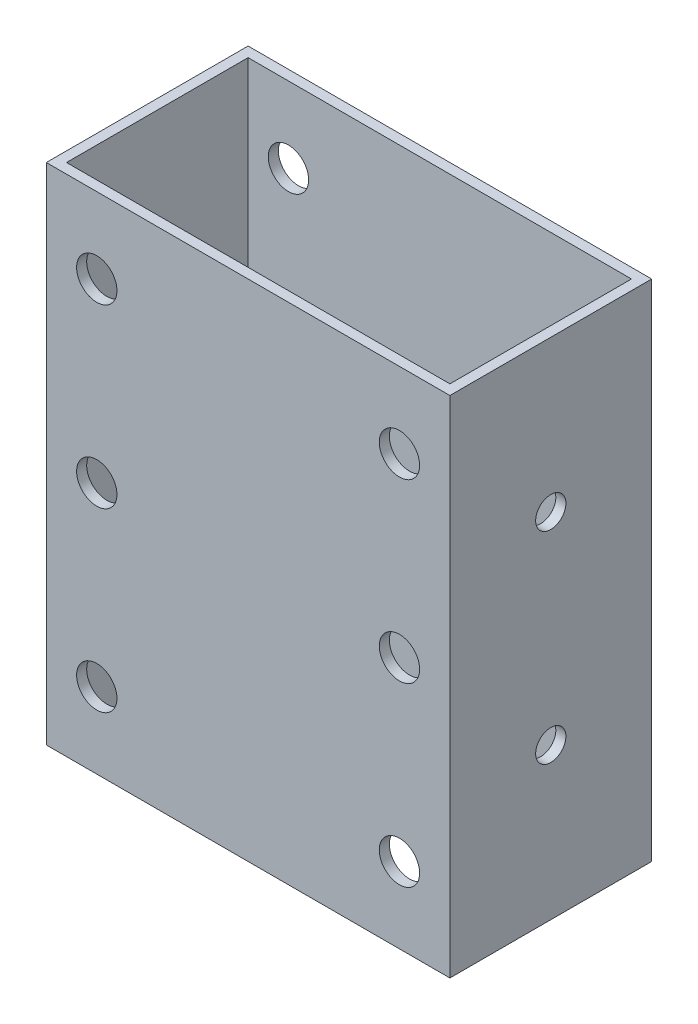
SolidWorks part; units mm, degrees
material "1060 Alloy"
ref_plane "Front" through (0, 0, 0) normal (0, 0, 1) x (1, 0, 0)
ref_plane "Top" through (0, 0, 0) normal (0, 1, 0) x (1, 0, 0)
ref_plane "Right" through (0, 0, 0) normal (1, 0, 0) x (0, 0, -1)
sketch "Sketch1" plane through (0, 0, 0) normal (0, 1, 0) x (1, 0, 0)
  line L0 (2, 2) -> (2, 38)
  line L1 (0, 0) -> (80, 0)
  line L2 (0, 0) -> (0, 40)
  line L3 (0, 40) -> (80, 40)
  line L4 (80, 0) -> (80, 40)
  line L5 (2, 38) -> (78, 38)
  line L6 (78, 2) -> (78, 38)
  line L7 (2, 2) -> (78, 2)
  dimension "D2" = 80
  dimension "D3" = 40
  dimension "D1" = 2
extrude "Boss-Extrude1" add sketch "Sketch1" along normal blind 100
sketch "Sketch2" plane through (0, 0, 0) normal (0, 0, 1) x (1, 0, 0)
  line L2 (0, 0) -> (80, 0) construction
  line L4 (0, 100) -> (0, 0) construction
  circle A0 centre (70, 15) radius 4
  circle A1 centre (70, 50) radius 4
  circle A2 centre (10, 15) radius 4
  circle A3 centre (70, 85) radius 4
  circle A4 centre (10, 50) radius 4
  circle A5 centre (10, 85) radius 4
  dimension "D3" = 3
  dimension "D4" = 60
  dimension "D5" = 35
  dimension "D6" = 8
  dimension "D1" = 10
  dimension "D2" = 2
  dimension "D7" = 15
extrude "Cut-Extrude1" cut sketch "Sketch2" against normal up to surface (40 mm away) up to face at (40, 50, -40)
sketch "Sketch3" plane through (0, 0, 0) normal (-1, 0, 0) x (0, 0, 1)
  line L0 (-40, 0) -> (0, 0) construction
  line L2 (-40, 100) -> (-40, 0) construction
  line L3 (-40, 50) -> (49960, 50) construction
  line L4 (0, 100) -> (0, 0) construction
  circle A0 centre (-20, 30) radius 3
  circle A1 centre (-20, 70) radius 3
  point P10 (-40, 50)
  point P13 (0, 50)
  dimension "D1" = 6
  dimension "D2" = 20
  dimension "D3" = 30
extrude "Cut-Extrude2" cut sketch "Sketch3" against normal up to surface (80 mm away) up to face at (80, 50, -20)
